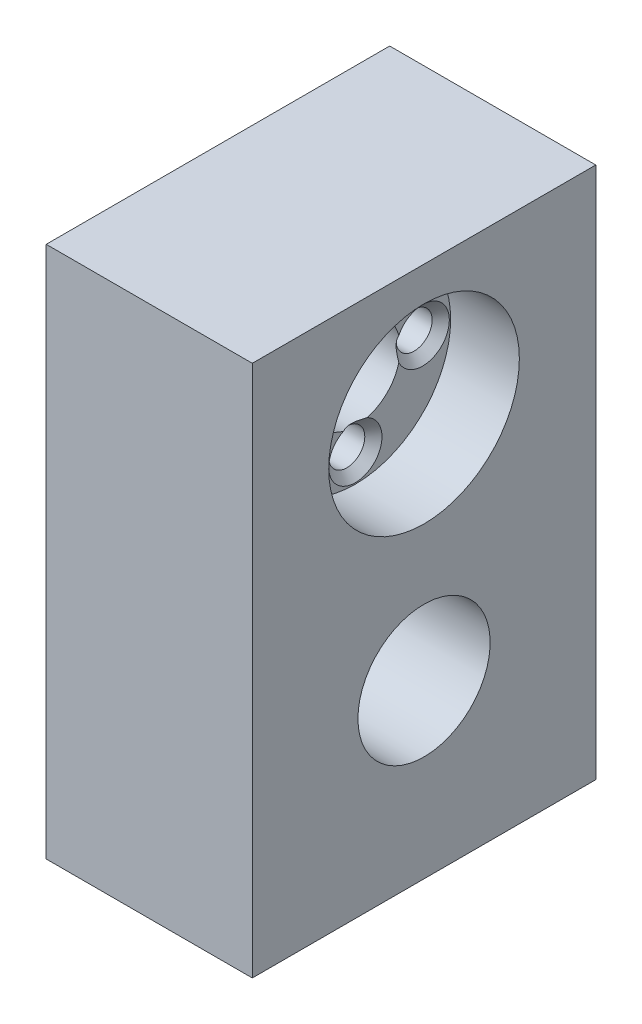
SolidWorks part; units mm, degrees
ref_plane "Front Plane" through (0, 0, 0) normal (0, 0, 1) x (1, 0, 0)
ref_plane "Top Plane" through (0, 0, 0) normal (0, 1, 0) x (1, 0, 0)
ref_plane "Right Plane" through (0, 0, 0) normal (1, 0, 0) x (0, 0, -1)
sketch "Sketch1" plane through (0, 0, 0) normal (0, 1, 0) x (1, 0, 0)
  line L0 (-12, -20) -> (-12, 20)
  line L1 (-12, -20) -> (12, -20)
  line L2 (-12, 20) -> (12, 20)
  line L3 (12, -20) -> (12, 20)
  line L4 (-12, -20) -> (12, 20) construction
  line L5 (-12, 20) -> (12, -20) construction
  point P1 (0, 0)
  dimension "D1" = 40
  dimension "D2" = 24
extrude "Boss-Extrude1" add sketch "Sketch1" along normal blind 62
sketch "Sketch2" plane through (-12, 0, 0) normal (-1, 0, 0) x (0, 0, 1)
  line L0 (-20, 0) -> (20, 0) construction
  circle A0 centre (0, 20) radius 16.2
  dimension "D1" = 32.4
  dimension "D2" = 20
extrude "Cut-Extrude1" cut sketch "Sketch2" against normal blind 5
sketch "Sketch3" plane through (-7, 0, 0) normal (-1, 0, 0) x (0, 0, 1)
  circle A0 centre (0, 20) radius 7.7
  dimension "D1" = 15.4
extrude "Cut-Extrude2" cut sketch "Sketch3" against normal blind 25
sketch "Sketch4" plane through (-7, 0, 0) normal (-1, 0, 0) x (0, 0, 1)
  line L0 (0, 36.2) -> (0, 27.7) construction
  circle A0 centre (0, 31.95) radius 2.1
  circle A1 centre (0, 20) radius 16.2 construction
  circle A2 centre (0, 20) radius 16.2 construction
  circle A3 centre (0, 20) radius 7.7 construction
  point P11 (0, 31.95)
  dimension "D1" = 4.2
extrude "Cut-Extrude3" cut sketch "Sketch4" against normal blind 6
chamfer "Chamfer1" distance 1 angle 45 1 edges at (-7, 31.95, 2.1)
pattern_circular "CirPattern1" count 4 over 360 about axis through (-7, 20, 0) along (-1, 0, 0) of "Cut-Extrude3", "Chamfer1"
sketch "Sketch5" plane through (12, 0, 0) normal (1, 0, 0) x (0, 0, -1)
  line L0 (-20, 62) -> (20, 62) construction
  circle A0 centre (0, 46.9) radius 11.1
  dimension "D1" = 22.2
  dimension "D2" = 15.1
extrude "Cut-Extrude4" cut sketch "Sketch5" against normal blind 8
sketch "Sketch6" plane through (4, 0, 0) normal (1, 0, 0) x (0, 0, -1)
  circle A0 centre (0, 46.9) radius 5.25
  dimension "D1" = 10.5
extrude "Cut-Extrude5" cut sketch "Sketch6" against normal up to surface (10.02 mm away)
sketch "Sketch7" plane through (-6.02, 0, 0) normal (1, 0, 0) x (0, 0, -1)
  circle A0 centre (0, 46.9) radius 4.2
  dimension "D1" = 8.4
extrude "Cut-Extrude6" cut sketch "Sketch7" against normal up to surface (5.98 mm away) up to face at (-12, 20, 16.2)
sketch "Sketch8" plane through (4, 0, 0) normal (1, 0, 0) x (0, 0, -1)
  circle A0 centre (0, 54.7452) radius 2.1
  dimension "D1" = 4.2
extrude "Cut-Extrude7" cut sketch "Sketch8" against normal blind 6
chamfer "Chamfer2" distance 1 angle 45 1 edges at (4, 54.7452, -2.1)
pattern_circular "CirPattern2" count 4 over 360 about axis through (-6.02, 46.9, 0) along (1, 0, 0) of "Chamfer2", "Cut-Extrude7"
